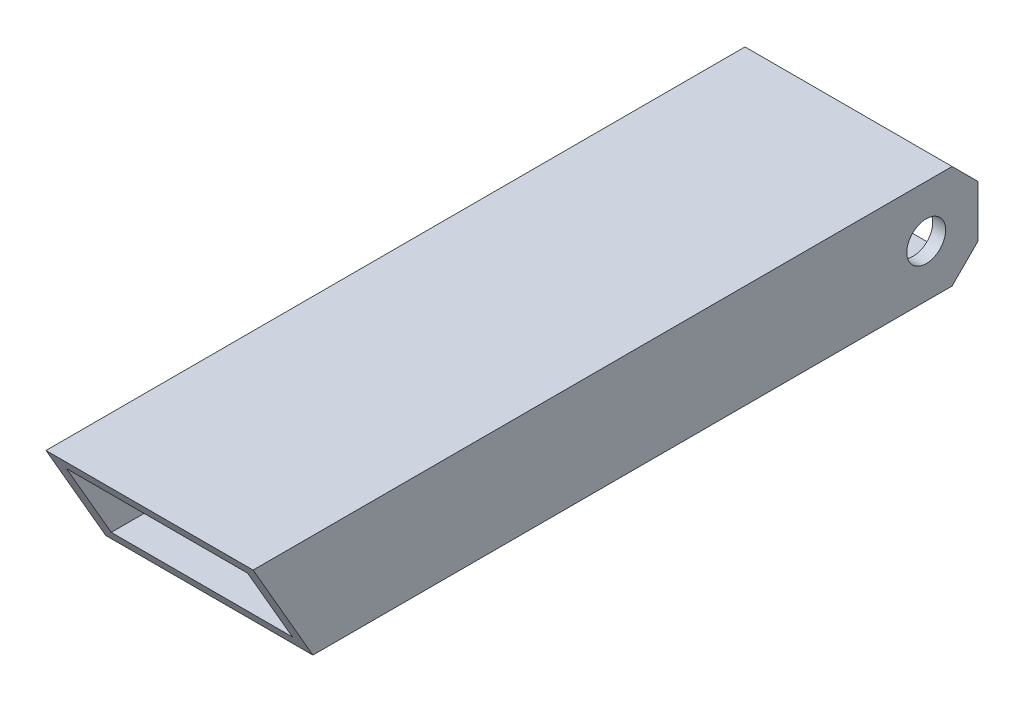
SolidWorks part; units mm, degrees
ref_plane "Front Plane" through (0, 0, 0) normal (0, 0, 1) x (1, 0, 0)
ref_plane "Top Plane" through (0, 0, 0) normal (0, 1, 0) x (1, 0, 0)
ref_plane "Right Plane" through (0, 0, 0) normal (1, 0, 0) x (0, 0, -1)
sketch "Sketch1" plane through (0, 0, 0) normal (0, 0, 1) x (1, 0, 0)
  line L0 (-22.225, 9.525) -> (22.225, 9.525)
  line L1 (-25.4, -12.7) -> (25.4, -12.7)
  line L2 (-25.4, -12.7) -> (-25.4, 12.7)
  line L3 (-25.4, 12.7) -> (25.4, 12.7)
  line L4 (25.4, -12.7) -> (25.4, 12.7)
  line L5 (-25.4, -12.7) -> (25.4, 12.7) construction
  line L6 (-25.4, 12.7) -> (25.4, -12.7) construction
  line L7 (22.225, -9.525) -> (22.225, 9.525)
  line L8 (-22.225, -9.525) -> (22.225, -9.525)
  line L9 (-22.225, -9.525) -> (-22.225, 9.525)
  point P0 (0, 0)
  dimension "D1" = 50.8
  dimension "D2" = 25.4
  dimension "D3" = 3.175
extrude "Boss-Extrude1" add sketch "Sketch1" along normal blind 177.8
sketch "Sketch2" plane through (25.4, 0, 0) normal (1, 0, 0) x (0, 0, -1)
  line L0 (-177.8, 12.7) -> (-163.1353, -12.7)
  line L1 (-177.8, -12.7) -> (0, -12.7) construction
  line L2 (-163.1353, -12.7) -> (-177.8, -12.7)
  line L3 (-177.8, -12.7) -> (-177.8, 12.7)
  dimension "D1" = 60
extrude "Cut-Extrude1" cut sketch "Sketch2" against normal through all
sketch "Sketch3" plane through (25.4, 0, 0) normal (1, 0, 0) x (0, 0, -1)
  line L0 (0, 0) -> (-170.4677, 0) construction
  line L1 (-163.1353, -12.7) -> (-177.8, 12.7) construction
  circle A0 centre (-12.7, 0) radius 4.7625
  dimension "D1" = 9.525
  dimension "D2" = 12.7
extrude "Cut-Extrude2" cut sketch "Sketch3" against normal through all
sketch "Sketch4" plane through (25.4, 0, 0) normal (1, 0, 0) x (0, 0, -1)
  line L0 (-6.35, 12.7) -> (0, 6.35)
  line L1 (-177.8, 12.7) -> (0, 12.7) construction
  line L2 (0, -12.7) -> (0, 12.7) construction
  line L3 (0, 6.35) -> (0, 12.7)
  line L4 (0, 12.7) -> (-6.35, 12.7)
  line L5 (0, 0) -> (-170.4677, 0) construction
  line L6 (-163.1353, -12.7) -> (-177.8, 12.7) construction
  line L7 (0, -12.7) -> (-6.35, -12.7)
  line L8 (0, -6.35) -> (0, -12.7)
  line L9 (-6.35, -12.7) -> (0, -6.35)
  dimension "D1" = 6.35
  dimension "D2" = 6.35
extrude "Cut-Extrude3" cut sketch "Sketch4" against normal through all
